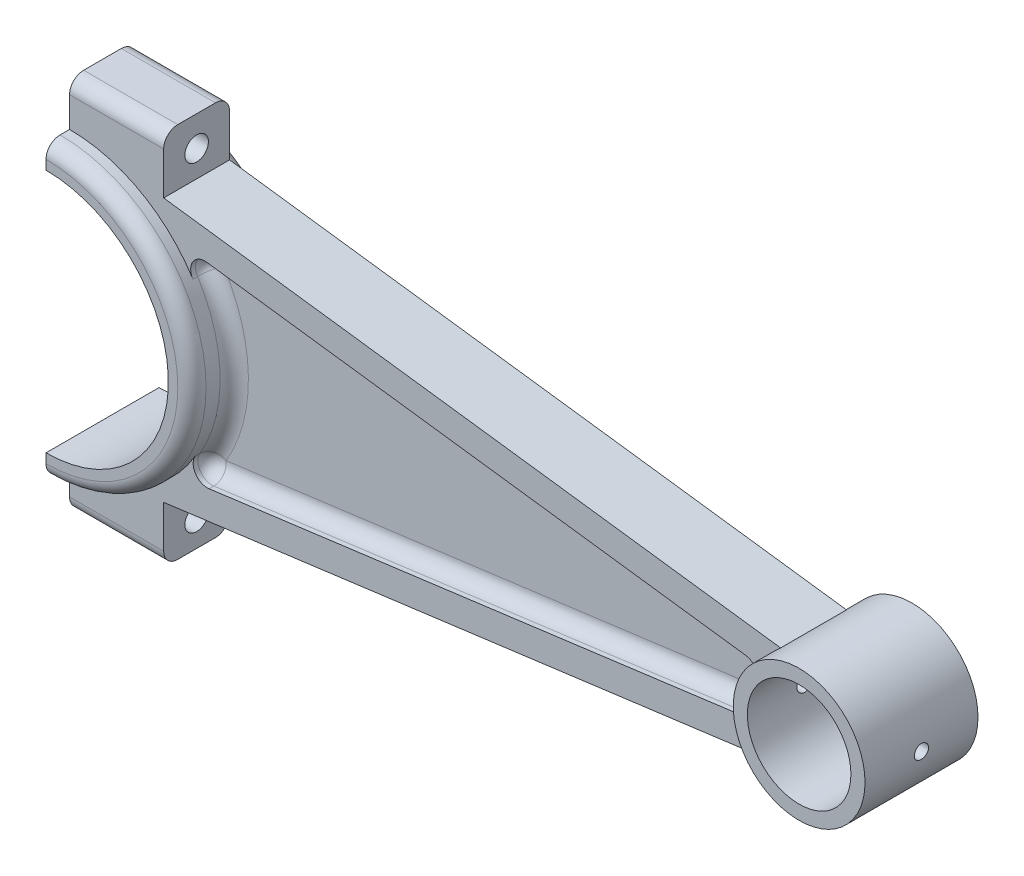
SolidWorks part; units mm, degrees
ref_plane "前视基准面" through (0, 0, 0) normal (0, 0, 1) x (1, 0, 0)
ref_plane "上视基准面" through (0, 0, 0) normal (0, 1, 0) x (1, 0, 0)
ref_plane "右视基准面" through (0, 0, 0) normal (1, 0, 0) x (0, 0, -1)
other "Configuration Table"
sketch "草图1" plane through (0, 0, 0) normal (0, 0, 1) x (1, 0, 0)
  line L0 (0, 31) -> (0, -31)
  arc A0 (0, 31) -> (0, -31) centre (0, 0) cw
  dimension "D1" = 31
extrude "凸台-拉伸1" add sketch "草图1" along normal mid plane 24
sketch "草图2" plane through (0, 0, 0) normal (0, 0, 1) x (1, 0, 0)
  line L1 (0, 40.3932) -> (174, 40.3932)
  line L2 (0, 40.3932) -> (0, -39.6068)
  line L3 (0, -39.6068) -> (174, -39.6068)
  line L4 (174, 40.3932) -> (174, -39.6068)
  dimension "D1" = 80
  dimension "D2" = 174
extrude "凸台-拉伸2" add sketch "草图2" along normal mid plane 14
sketch "草图4" plane through (0, 0, 0) normal (0, 0, 1) x (1, 0, 0)
  line L0 (0, 31) -> (0, -31) construction
  line L1 (0, 26) -> (0, -26)
  arc A0 (0, 26) -> (0, -26) centre (0, 0) cw
  dimension "D1" = 26
extrude "切除-拉伸1" cut sketch "草图4" against normal through all both and the other way through all
sketch "草图5" plane through (0, 0, 0) normal (0, 0, 1) x (1, 0, 0)
  line L0 (0, 0) -> (174, 0.3932) construction
  line L1 (174, -39.6068) -> (174, 40.3932) construction
  circle A0 centre (160, 0.3615) radius 14
  dimension "D1" = 28
extrude "凸台-拉伸5" add sketch "草图5" along normal mid plane 24
sketch "草图11" plane through (0, 0, 12) normal (0, 0, 1) x (1, 0, 0)
  circle A0 centre (160, 0.3615) radius 11
  dimension "D1" = 22
extrude "切除-拉伸2" cut sketch "草图11" against normal through all both and the other way through all
sketch "草图12" plane through (0, 0, 0) normal (0, 0, 1) x (1, 0, 0)
  line L0 (20, -27.6068) -> (150.9981, -10.3606)
  line L1 (0, -39.6068) -> (20, -39.6068)
  line L2 (0, -39.6068) -> (0, -27.6068)
  line L3 (0, -27.6068) -> (20, -27.6068)
  line L4 (20, -39.6068) -> (20, -27.6068)
  line L5 (150.9981, -10.3606) -> (20, -27.6068)
  line L6 (174, 0.3615) -> (174, -39.6068)
  line L7 (174, -39.6068) -> (20, -39.6068)
  line L8 (20, -27.6068) -> (20, -39.6068)
  arc A0 (174, 0.3932) -> (174, 0.3299) centre (160, 0.3615) ccw construction
  arc A1 (150.9981, -10.3606) -> (174, 0.3615) centre (160, 0.3615) ccw
  circle A2 centre (160, 0.3615) radius 14 construction
  dimension "D1" = 20
  dimension "D2" = 12
extrude "切除-拉伸3" cut sketch "草图12" against normal through all both and the other way through all contours A1 L0 L4 L7 L6 region at (107.8489, -28.0521, 0)
sketch "草图13" plane through (0, 0, 0) normal (0, 0, 1) x (1, 0, 0)
  line L0 (20, 28.3932) -> (151.0636, 11.1383)
  line L1 (0, 40.3932) -> (20, 40.3932)
  line L2 (0, 40.3932) -> (0, 28.3932)
  line L3 (0, 28.3932) -> (20, 28.3932)
  line L4 (20, 40.3932) -> (20, 28.3932)
  line L5 (151.0636, 11.1383) -> (20, 28.3932)
  line L6 (174, 0.3932) -> (174, 40.3932) construction
  line L7 (174, 0.3932) -> (174, 40.3932)
  line L8 (174, 40.3932) -> (20, 40.3932)
  circle A0 centre (160, 0.3615) radius 14 construction
  arc A1 (151.0636, 11.1383) -> (174, 0.3932) centre (160, 0.3615) cw
  dimension "D1" = 20
  dimension "D2" = 12
  dimension "D3" = 7.5
extrude "切除-拉伸4" cut sketch "草图13" against normal through all both and the other way through all contours L0 A1 L7 L8 L4 region at (107.8726, 28.8313, 0)
sketch "草图14" plane through (0, 0, 0) normal (0, 0, 1) x (1, 0, 0)
  line L0 (21.7245, 22.1144) -> (147.0244, 5.6183)
  line L1 (147.0244, 5.6183) -> (21.7245, 22.1144)
  line L2 (20, 28.3932) -> (151.0636, 11.1383) construction
  line L3 (22.6065, -21.2119) -> (147.0003, -4.8351)
  line L4 (147.0003, -4.8351) -> (22.6065, -21.2119)
  line L5 (20, -27.6068) -> (150.9981, -10.3606) construction
  arc A0 (0, -31) -> (0, 31) centre (0, 0) ccw construction
  circle A1 centre (160, 0.3615) radius 14 construction
  arc A2 (151.0636, 11.1383) -> (150.9981, -10.3606) centre (160, 0.3615) ccw construction
  arc A3 (21.7245, 22.1144) -> (22.6065, -21.2119) centre (0, 0) cw
  arc A4 (147.0244, 5.6183) -> (147.0053, -4.8477) centre (160, 0.3615) ccw
  dimension "D1" = 6
  dimension "D2" = 6
extrude "切除-拉伸6" cut sketch "草图14" against normal through all both and the other way through all contours A4 L0 A3 L3 region at (75.634, 0.4268, 0)
sketch "草图17" plane through (0, 0, 0) normal (0, 0, 1) x (1, 0, 0)
  line L0 (21.7245, 22.1144) -> (147.0244, 5.6183)
  line L1 (147.0003, -4.8351) -> (22.6065, -21.2119)
  arc A0 (147.0244, 5.6183) -> (147.0003, -4.8351) centre (160, 0.3615) ccw
  arc A1 (147.0003, -4.8351) -> (150.9981, -10.3606) centre (160, 0.3615) ccw construction
  arc A2 (22.6065, -21.2119) -> (21.7245, 22.1144) centre (0, 0) ccw
extrude "凸台-拉伸6" add sketch "草图17" along normal mid plane 6 contours A2 L1 A0 L0 region at (75.634, 0.4268, 0)
sketch "草图19" plane through (0, 0, 0) normal (1, 0, 0) x (0, 0, -1)
  circle A0 centre (0, 34) radius 2.5
  dimension "D1" = 5
  dimension "D2" = 34
extrude "切除-拉伸7" cut sketch "草图19" against normal through all both and the other way through all
sketch "草图20" plane through (20, 0, 0) normal (1, 0, 0) x (0, 0, -1)
  circle A0 centre (0, -34) radius 2.5
  dimension "D1" = 5
  dimension "D2" = 34
extrude "切除-拉伸8" cut sketch "草图20" against normal through all both and the other way through all
sketch "草图21" plane through (0, 0, 0) normal (1, 0, 0) x (0, 0, -1)
  circle A0 centre (0, 0) radius 1.5
  dimension "D1" = 3
extrude "切除-拉伸9" cut sketch "草图21" against normal through all both and the other way through all
fillet "圆角1" radius 3 4 edges at (10, -39.6068, -7) (10, -39.6068, 7) (10, 40.3932, -7) (10, 40.3932, 7)
fillet "圆角2" radius 3 2 edges at (31, 0, -12) (31, 0, 12)
fillet "圆角3" radius 3 4 edges at (21.7245, 22.1144, -5) (22.6065, -21.2119, -5) (22.6065, -21.2119, 5) (21.7245, 22.1144, 5)
fillet "圆角4" radius 3 4 edges at (147.0244, 5.6183, -5) (147.0003, -4.8351, -5) (147.0003, -4.8351, 5) (147.0244, 5.6183, 5)
fillet "圆角5" radius 3 8 edges at (26.7608, -18.9631, 3) (86.629, -12.7832, 3) (145.6153, -4.1024, 3) (146.0001, 0.3874, 3) (145.6286, 4.883, 3) (86.3725, 13.6033, 3) (26.2137, 19.7812, 3) (30.9966, 0.457, 3)
fillet "圆角6" radius 3 8 edges at (26.7608, -18.9631, -3) (86.629, -12.7832, -3) (145.6153, -4.1024, -3) (146.0001, 0.3874, -3) (145.6286, 4.883, -3) (86.3725, 13.6033, -3) (26.2137, 19.7812, -3) (30.9966, 0.457, -3)
